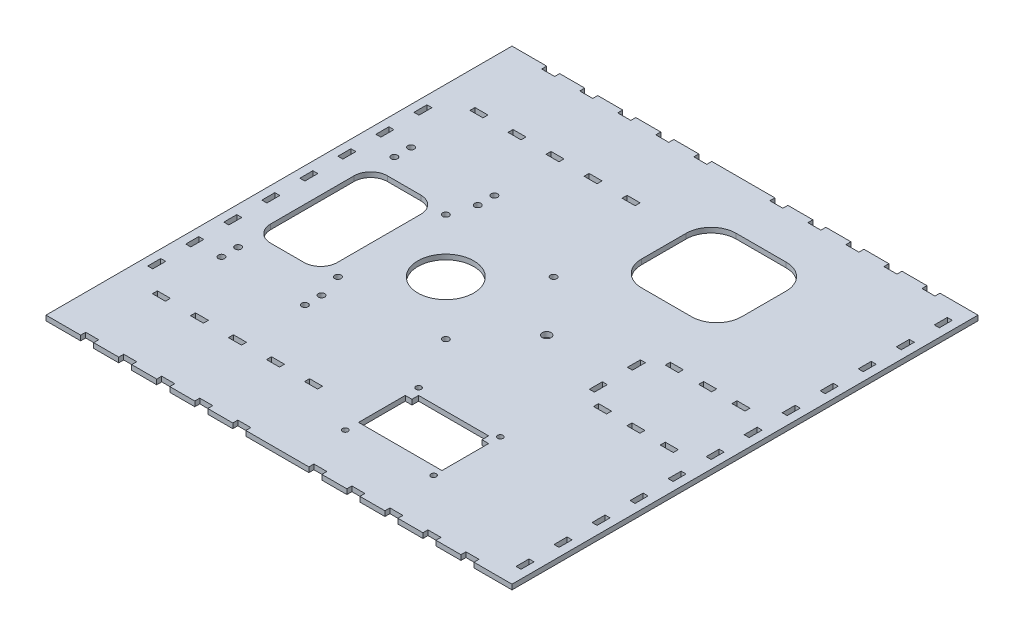
SolidWorks part; units mm, degrees
material "ENPH 253 Hardboard"
ref_plane "Front Plane" through (0, 0, 0) normal (0, 0, 1) x (1, 0, 0)
ref_plane "Top Plane" through (0, 0, 0) normal (0, 1, 0) x (1, 0, 0)
ref_plane "Right Plane" through (0, 0, 0) normal (1, 0, 0) x (0, 0, -1)
sketch "Sketch1" plane through (0, 0, 0) normal (0, 1, 0) x (1, 0, 0)
  line L0 (0, -139.7) -> (0, 139.7) construction
  line L1 (-139.7, 139.7) -> (139.7, 139.7)
  line L2 (-139.7, 139.7) -> (-139.7, -139.7)
  line L3 (-139.7, -139.7) -> (139.7, -139.7)
  line L4 (139.7, 139.7) -> (139.7, -139.7)
  line L5 (-139.7, 139.7) -> (139.7, -139.7) construction
  line L6 (-139.7, -139.7) -> (139.7, 139.7) construction
  line L12 (-139.7, 0) -> (139.7, 0) construction
  point P0 (0, 0)
  dimension "D1" = 279.4
  dimension "D2" = 279.4
extrude "Boss-Extrude1" add sketch "Sketch1" along normal blind 3
sketch "Sketch3" plane through (0, 0, 0) normal (0, -1, 0) x (-1, 0, 0)
  line L0 (-139.7, -139.7) -> (-139.7, 139.7) construction
  line L1 (-134.7, 129.3) -> (-131.7, 129.3)
  line L2 (-134.7, 129.3) -> (-134.7, 121.5)
  line L3 (-134.7, 121.5) -> (-131.7, 121.5)
  line L4 (-131.7, 129.3) -> (-131.7, 121.5)
  line L5 (-139.7, 139.7) -> (139.7, 139.7) construction
  dimension "D1" = 5
  dimension "D2" = 10.4
  dimension "D3" = 7.8
  dimension "D4" = 3
extrude "Cut-Extrude2" cut sketch "Sketch3" against normal through all
pattern_linear "LPattern1" count 12 spacing 22.8 along (0, 0, 1) of "Cut-Extrude2"
sketch "Sketch5" plane through (0, 0, 0) normal (0, -1, 0) x (1, 0, 0)
  line L0 (139.7, -139.7) -> (-139.7, -139.7) construction
  line L1 (109.1, -139.7) -> (116.9, -139.7)
  line L2 (109.1, -139.7) -> (109.1, -136.7)
  line L3 (109.1, -136.7) -> (116.9, -136.7)
  line L4 (116.9, -139.7) -> (116.9, -136.7)
  line L5 (139.7, 139.7) -> (139.7, -139.7) construction
  dimension "D1" = 22.8
  dimension "D2" = 7.8
  dimension "D3" = 3
extrude "Cut-Extrude3" cut sketch "Sketch5" against normal through all
pattern_linear "LPattern2" count 11 spacing 22.8 along (-1, 0, 0) skipping (5, 0) of "Cut-Extrude3"
mirror "Mirror2" about plane through (0, 0, 0) normal (0, 0, 1) of "LPattern2"
sketch "Sketch6" plane through (0, 0, 0) normal (0, -1, 0) x (1, 0, 0)
  line L0 (63.5, -139.7) -> (48.5, -139.7) construction
  line L1 (-134.7, -83.7) -> (-131.7, -83.7)
  line L2 (-134.7, -83.7) -> (-134.7, -75.9)
  line L3 (-134.7, -75.9) -> (-131.7, -75.9)
  line L4 (-131.7, -83.7) -> (-131.7, -75.9)
  line L5 (-139.7, -139.7) -> (-139.7, 139.7) construction
  dimension "D1" = 56
  dimension "D2" = 5
  dimension "D3" = 3
  dimension "D4" = 7.8
extrude "Cut-Extrude4" cut sketch "Sketch6" against normal through all
pattern_linear "LPattern3" count 8 spacing 22.8 along (0, 0, 1) of "Cut-Extrude4"
sketch "Sketch7" plane through (0, 0, 0) normal (0, -1, 0) x (-1, 0, 0)
  line L1 (139.7, 139.7) -> (139.7, -139.7) construction
  line L3 (-63.5, 139.7) -> (-48.5, 139.7) construction
  circle A0 centre (39.7, 0) radius 16.75
  dimension "D1" = 33.5
  dimension "D2" = 100
  dimension "D3" = 139.7
extrude "Cut-Extrude5" cut sketch "Sketch7" against normal through all
hole_wizard "#6 Clearance Hole1" positions "Sketch8" profile "Sketch9" hole size "#6" standard "ANSI Inch" end condition through all
sketch "Sketch8" plane through (0, 3, 0) normal (0, 1, 0) x (1, 0, 0)
  line L0 (-72.025, -32.325) -> (-72.025, 32.325) construction
  line L1 (-72.025, 32.325) -> (-7.375, 32.325) construction
  line L2 (-7.375, 32.325) -> (-7.375, -32.325) construction
  line L3 (-7.375, -32.325) -> (-72.025, -32.325) construction
  point P0 (-72.025, -32.325)
  point P2 (-72.025, 32.325)
  point P4 (-7.375, 32.325)
  point P6 (-7.375, -32.325)
  dimension "D1" = 64.65
  dimension "D2" = 64.65
  dimension "D3" = 90
  dimension "D4" = 64.65
  dimension "D5" = 32.325
  dimension "D6" = 32.325
sketch "Sketch9" plane through (-72.025, 3, 32.325) normal (1, 0, 0) x (0, 0, 1)
  line L0 (0, 0) -> (0, 3)
  line L1 (0, 3) -> (1.8986, 3)
  line L2 (1.8986, 3) -> (1.8986, 0)
  line L5 (1.8986, 0) -> (0, 0)
  line L11 (0, -6.35) -> (0, 107.95) construction
  dimension "Thru Hole Dia." = 3.7973
  dimension "Thru Hole Depth" = 3
hole_wizard "#6 Clearance Hole2" positions "Sketch10" profile "Sketch11" hole size "#6" standard "ANSI Inch" end condition through all
sketch "Sketch10" plane through (0, 3, 0) normal (0, 1, 0) x (1, 0, 0)
  line L1 (-118.9, 139.7) -> (-139.7, 139.7) construction
  line L2 (-139.7, -139.7) -> (-118.9, -139.7) construction
  line L3 (-73.3, 139.7) -> (-88.3, 139.7) construction
  line L4 (-88.3, -139.7) -> (-73.3, -139.7) construction
  line L5 (-139.7, 139.7) -> (-139.7, -139.7) construction
  point P0 (-117.36, 56.83)
  point P2 (-67.36, 56.83)
  point P4 (-117.36, -56.83)
  point P6 (-67.36, -56.83)
  point P22 (-67.36, -46.83)
  point P24 (-117.36, -46.83)
  point P26 (-67.36, 46.83)
  point P28 (-117.36, 46.83)
  dimension "D2" = 50
  dimension "D3" = 22.34
  dimension "D4" = 50
  dimension "D5" = 82.87
  dimension "D6" = 82.87
  dimension "D7" = 82.87
  dimension "D8" = 82.87
  dimension "D9" = 10
  dimension "D10" = 10
  dimension "D11" = 50
  dimension "D12" = 10
  dimension "D13" = 10
  dimension "D14" = 50
  dimension "D15" = 22.34
  dimension "D16" = 22.34
  dimension "D17" = 22.34
sketch "Sketch11" plane through (-117.36, 3, -56.83) normal (1, 0, 0) x (0, 0, 1)
  line L0 (0, 0) -> (0, 3)
  line L1 (0, 3) -> (1.8986, 3)
  line L2 (1.8986, 3) -> (1.8986, 0)
  line L5 (1.8986, 0) -> (0, 0)
  line L11 (0, -6.35) -> (0, 107.95) construction
  dimension "Thru Hole Dia." = 3.7973
  dimension "Thru Hole Depth" = 3
sketch "Sketch14" plane through (0, 0, 0) normal (0, -1, 0) x (-1, 0, 0)
  line L0 (139.7, 139.7) -> (139.7, -139.7) construction
  line L1 (-17.9, 139.7) -> (19.9, 139.7) construction
  circle A0 centre (-20.8, 0) radius 2.65
  dimension "D1" = 5.3
  dimension "D2" = 160.5
  dimension "D3" = 139.7
extrude "Cut-Extrude6" cut sketch "Sketch14" against normal through all
sketch "Sketch16" plane through (0, 0, 0) normal (0, -1, 0) x (1, 0, 0)
  line L0 (-139.7, -139.7) -> (-139.7, 139.7) construction
  line L1 (-118.9, 96.7) -> (-111.1, 96.7)
  line L2 (-118.9, 96.7) -> (-118.9, 93.7)
  line L3 (-118.9, 93.7) -> (-111.1, 93.7)
  line L4 (-111.1, 96.7) -> (-111.1, 93.7)
  line L7 (-111.1, 136.7) -> (-118.9, 136.7) construction
  dimension "D1" = 20.8
  dimension "D2" = 7.8
  dimension "D3" = 40
  dimension "D4" = 3
extrude "Cut-Extrude8" cut sketch "Sketch16" against normal through all
pattern_linear "LPattern5" count 5 spacing 22.8 along (1, 0, 0) of "Cut-Extrude8"
mirror "Mirror4" about plane through (0, 0, 0) normal (0, 0, 1) of "LPattern5"
sketch "Sketch17" plane through (0, 0, 0) normal (0, -1, 0) x (1, 0, 0)
  line L1 (119.7, 23) -> (111.9, 23)
  line L2 (119.7, 23) -> (119.7, 20)
  line L3 (119.7, 20) -> (111.9, 20)
  line L4 (111.9, 23) -> (111.9, 20)
  line L5 (94.1, 139.7) -> (109.1, 139.7) construction
  line L6 (139.7, 139.7) -> (139.7, -139.7) construction
  point P8 (119.7, 21.5)
  dimension "D1" = 116.7
  dimension "D2" = 20
  dimension "D3" = 7.8
  dimension "D4" = 3
extrude "Cut-Extrude9" cut sketch "Sketch17" against normal through all
pattern_linear "LPattern6" count 3 spacing 20 along (-1, 0, 0) of "Cut-Extrude9"
sketch "Sketch18" plane through (0, 0, 0) normal (0, -1, 0) x (-1, 0, 0)
  line L0 (-139.7, -139.7) -> (-139.7, 139.7) construction
  line L1 (-64.7, -15.3) -> (-61.7, -15.3)
  line L2 (-64.7, -15.3) -> (-64.7, -7.5)
  line L3 (-64.7, -7.5) -> (-61.7, -7.5)
  line L4 (-61.7, -15.3) -> (-61.7, -7.5)
  line L5 (-71.3, -139.7) -> (-86.3, -139.7) construction
  dimension "D1" = 7.8
  dimension "D2" = 3
  dimension "D3" = 75
  dimension "D4" = 124.4
extrude "Cut-Extrude10" cut sketch "Sketch18" against normal through all
mirror "Mirror5" about plane through (0, 0, 0) normal (0, 0, 1) of "Cut-Extrude10", "LPattern6", "Cut-Extrude9"
sketch "Sketch19" plane through (0, 0, 0) normal (0, -1, 0) x (1, 0, 0)
  line L0 (0, 0) -> (139.7, 0) construction
  line L1 (24.7, -109.7) -> (54.7, -109.7)
  line L2 (9.7, -94.7) -> (9.7, -68)
  line L3 (24.7, -53) -> (54.7, -53)
  line L4 (69.7, -94.7) -> (69.7, -68)
  line L9 (139.7, 139.7) -> (139.7, -139.7) construction
  line L10 (86.3, -139.7) -> (71.3, -139.7) construction
  line L11 (79.7, -23) -> (71.9, -23) construction
  line L16 (-139.7, -139.7) -> (-139.7, 139.7) construction
  line L17 (-89.7, 35) -> (-109.7, 35)
  line L18 (-79.7, 25) -> (-79.7, -25)
  line L19 (-89.7, -35) -> (-109.7, -35)
  line L20 (-119.7, 25) -> (-119.7, -25)
  line L21 (9.7, 101.7) -> (59.7, 101.7)
  line L22 (9.7, 65.7) -> (59.7, 65.7) construction
  line L23 (9.7, 65.7) -> (9.7, 109.7) construction
  line L24 (9.7, 109.7) -> (59.7, 109.7) construction
  line L25 (59.7, 65.7) -> (59.7, 109.7) construction
  line L29 (13.7, 69.7) -> (55.7, 69.7)
  line L30 (25.7, 139.7) -> (40.7, 139.7) construction
  line L32 (59.7, 101.7) -> (59.7, 73.7) construction
  line L34 (9.7, 101.7) -> (9.7, 73.7) construction
  line L35 (139.7, 139.7) -> (139.7, -139.7) construction
  line L38 (9.7, 101.7) -> (9.7, 73.7)
  line L39 (9.7, 73.7) -> (13.7, 73.7)
  line L40 (13.7, 73.7) -> (13.7, 69.7)
  line L41 (55.7, 69.7) -> (55.7, 73.7)
  line L42 (55.7, 73.7) -> (59.7, 73.7)
  line L43 (59.7, 73.7) -> (59.7, 101.7)
  line L48 (13.7, 69.7) -> (13.7, 105.7) construction
  line L49 (13.7, 105.7) -> (55.7, 105.7) construction
  line L50 (55.7, 69.7) -> (55.7, 105.7) construction
  arc A1 (54.7, -53) -> (69.7, -68) centre (54.7, -68) cw
  arc A2 (54.7, -109.7) -> (69.7, -94.7) centre (54.7, -94.7) ccw
  arc A3 (24.7, -109.7) -> (9.7, -94.7) centre (24.7, -94.7) cw
  arc A4 (9.7, -68) -> (24.7, -53) centre (24.7, -68) cw
  circle A9 centre (-39.7, 0) radius 16.75 construction
  arc A10 (-79.7, -25) -> (-89.7, -35) centre (-89.7, -25) cw
  arc A11 (-89.7, 35) -> (-79.7, 25) centre (-89.7, 25) cw
  arc A12 (-109.7, 35) -> (-119.7, 25) centre (-109.7, 25) ccw
  arc A13 (-109.7, -35) -> (-119.7, -25) centre (-109.7, -25) cw
  point P43 (-79.7, -35)
  point P46 (-79.7, 35)
  dimension "D9" = 35
  dimension "D10" = 10
  dimension "D11" = 44
  dimension "D12" = 50
  dimension "D1" = 15
  dimension "D2" = 30
  dimension "D3" = 70
  dimension "D4" = 30
  dimension "D5" = 60
  dimension "D6" = 70
  dimension "D7" = 20
  dimension "D8" = 40
  dimension "D17" = 30
  dimension "D18" = 80
  dimension "D14" = 4
extrude "Cut-Extrude11" cut sketch "Sketch19" against normal through all
hole_wizard "#4 Clearance Hole1" positions "Sketch20" profile "Sketch21" hole size "#4" standard "ANSI Inch" end condition through all
sketch "Sketch20" plane through (0, 3, 0) normal (0, 1, 0) x (1, 0, 0)
  line L0 (9.7, -101.7) -> (9.7, -73.7) construction
  line L1 (59.7, -73.7) -> (59.7, -101.7) construction
  point P0 (9.7, -65.7)
  point P2 (59.7, -66.7)
  point P4 (59.7, -106.7)
  point P6 (9.7, -109.7)
  point P7 (0, 0)
  point P10 (0, 0)
  point P13 (0, 0)
  point P15 (0, 0)
  point P16 (0, 0)
  point P17 (0, 0)
  point P18 (0, 0)
  point P19 (0, 0)
  point P22 (0, 0)
  dimension "D1" = 8
  dimension "D2" = 8
  dimension "D3" = 5
  dimension "D4" = 1
sketch "Sketch21" plane through (9.7, 3, 65.7) normal (1, 0, 0) x (0, 0, 1)
  line L0 (0, 0) -> (0, 3)
  line L1 (0, 3) -> (1.6319, 3)
  line L2 (1.6319, 3) -> (1.6319, 0)
  line L5 (1.6319, 0) -> (0, 0)
  line L11 (0, -6.35) -> (0, 107.95) construction
  dimension "Thru Hole Dia." = 3.2639
  dimension "Thru Hole Depth" = 3
equation "\"45mmm\"=50"
